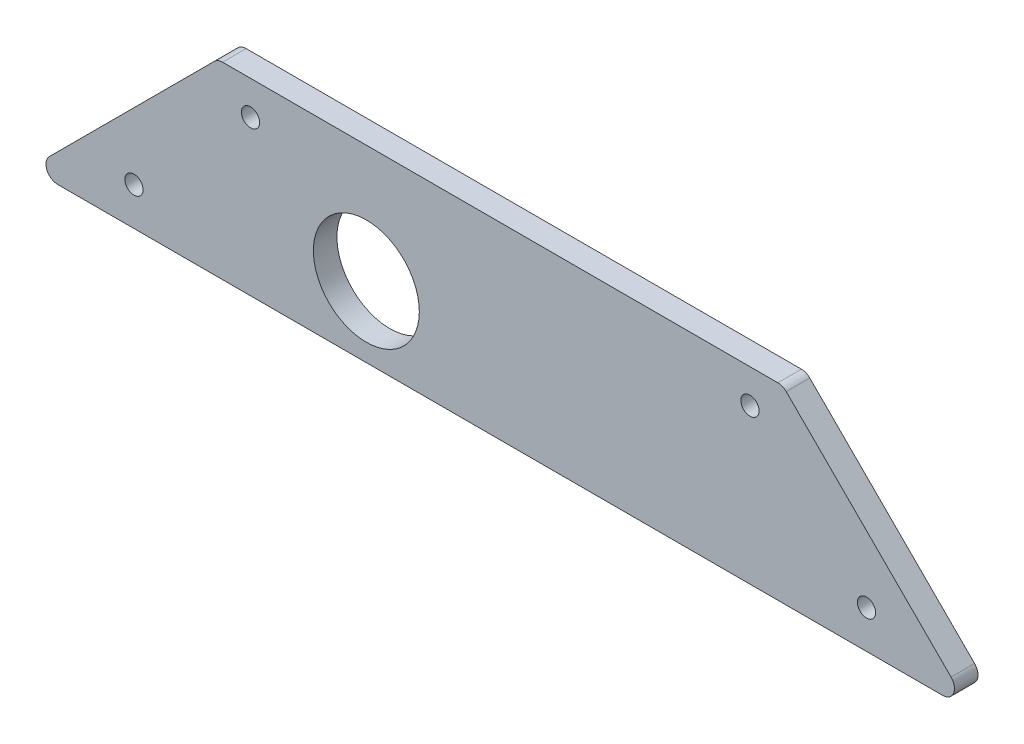
SolidWorks part; units mm, degrees
ref_plane "Front Plane" through (0, 0, 0) normal (0, 0, 1) x (1, 0, 0)
ref_plane "Top Plane" through (0, 0, 0) normal (0, 1, 0) x (1, 0, 0)
ref_plane "Right Plane" through (0, 0, 0) normal (1, 0, 0) x (0, 0, -1)
sketch "Sketch1" plane through (0, 0, 0) normal (0, 0, 1) x (1, 0, 0)
  line L0 (-76.2, 29.1622) -> (-127, -21.6378)
  line L1 (-76.2, 29.1622) -> (76.2, 29.1622)
  line L2 (-127, -21.6378) -> (127, -21.6378)
  line L3 (127, -21.6378) -> (76.2, 29.1622)
  point P0 (0, 0)
  point P1 (0, -21.6378)
  dimension "D1" = 135
  dimension "D2" = 254
  dimension "D3" = 50.8
  dimension "D4" = 135
extrude "Boss-Extrude1" add sketch "Sketch1" along normal mid plane 6.35
sketch "Sketch2" plane through (0, 0, 3.175) normal (0, 0, 1) x (1, 0, 0)
  line L0 (-127, -21.6378) -> (127, -21.6378) construction
  line L3 (-76.2, 29.1622) -> (-127, -21.6378) construction
  circle A0 centre (-36.108, -2.5878) radius 14.2875
  dimension "D1" = 19.05
  dimension "D2" = 28.575
  dimension "D3" = 50.8
extrude "Cut-Extrude1" cut sketch "Sketch2" against normal through all
sketch "Sketch8" plane through (0, 0, 3.175) normal (0, 0, 1) x (1, 0, 0)
  line L0 (0, 105.3622) -> (-327.0287, -221.6666) construction
  line L1 (0, 69.4411) -> (279.7642, -210.3231) construction
  line L2 (76.2, 29.1622) -> (297.7247, -192.3626) construction
  line L3 (0, 69.4411) -> (-309.0682, -239.6271) construction
  line L4 (76.2, 29.1622) -> (0, 105.3622) construction
  line L5 (14.5597, 84.0009) -> (-309.0682, -239.6271) construction
  line L6 (58.2395, 11.2016) -> (279.7642, -210.3231) construction
  line L7 (-3.4008, 101.9614) -> (-327.0287, -221.6666) construction
  line L8 (98.7828, -11.3812) -> (67.3519, 20.0497) construction
  line L9 (-76.2, 29.1622) -> (-127, -21.6378) construction
  point P2 (67.3519, 20.0497)
  point P6 (98.7828, -11.3812)
  point P16 (-67.3519, 20.0497)
  point P18 (-98.7828, -11.3812)
  dimension "D1" = 25.4
  dimension "D2" = 25.4
  dimension "D3" = 12.7
  dimension "D4" = 107.95
  dimension "D5" = 44.45
  dimension "D6" = 12.7
  dimension "D7" = 12.7
  dimension "D8" = 107.95
  dimension "D9" = 12.7
  dimension "D10" = 44.45
hole_wizard "#10 (0.1935) Diameter Hole2" positions "3DSketch1" profile "Sketch9" hole size "#10" standard "ANSI Inch" end condition through all
sketch3d "3DSketch1"
  line L0 (-127, -21.6378, 3.175) -> (-76.2, 29.1622, 3.175) construction
  line L2 (-76.2, 29.1622, 3.175) -> (0, 105.3622, 3.175) construction
  line L3 (0, 105.3622, 3.175) -> (145.7507, -40.3886, 3.175) construction
  line L4 (76.2, 29.1622, 3.175) -> (297.7247, -192.3626, 3.175) construction
  line L5 (145.7507, -40.3886, 3.175) -> (127.7902, -58.3491, 3.175) construction
  line L6 (0, 69.4411, 3.175) -> (279.7642, -210.3231, 3.175) construction
  line L7 (127.7902, -58.3491, 3.175) -> (0, 69.4411, 3.175) construction
  line L8 (0, 69.4411, 3.175) -> (-116.7666, -47.3254, 3.175) construction
  line L9 (0, 69.4411, 3.175) -> (-309.0682, -239.6271, 3.175) construction
  line L10 (-116.7666, -47.3254, 3.175) -> (-134.7271, -29.3649, 3.175) construction
  line L11 (0, 105.3622, 3.175) -> (-327.0287, -221.6666, 3.175) construction
  line L12 (-134.7271, -29.3649, 3.175) -> (-127, -21.6378, 3.175) construction
  point P0 (67.3519, 20.0497, 3.175)
  point P4 (98.7828, -11.3812, 3.175)
  point P8 (-67.3519, 20.0497, 3.175)
  point P34 (-98.7828, -11.3812, 3.175)
  dimension "D1" = 12.7
  dimension "D2" = 107.95
  dimension "D3" = 12.7
  dimension "D6" = 12.7
  dimension "D4" = 107.95
  dimension "D5" = 44.45
sketch "Sketch9" plane through (67.3519, 20.0497, 3.175) normal (1, 0, 0) x (0, -1, 0)
  line L0 (0, 0) -> (0, 6.35)
  line L1 (0, 6.35) -> (2.4574, 6.35)
  line L2 (2.4574, 6.35) -> (2.4574, 0)
  line L5 (2.4574, 0) -> (0, 0)
  line L11 (0, -6.35) -> (0, 107.95) construction
  dimension "Thru Hole Dia." = 4.9149
  dimension "Thru Hole Depth" = 6.35
fillet "Fillet1" radius 3.175 4 edges at (-127, -21.6378, 0) (-76.2, 29.1622, 0) (127, -21.6378, 0) (76.2, 29.1622, 0)
